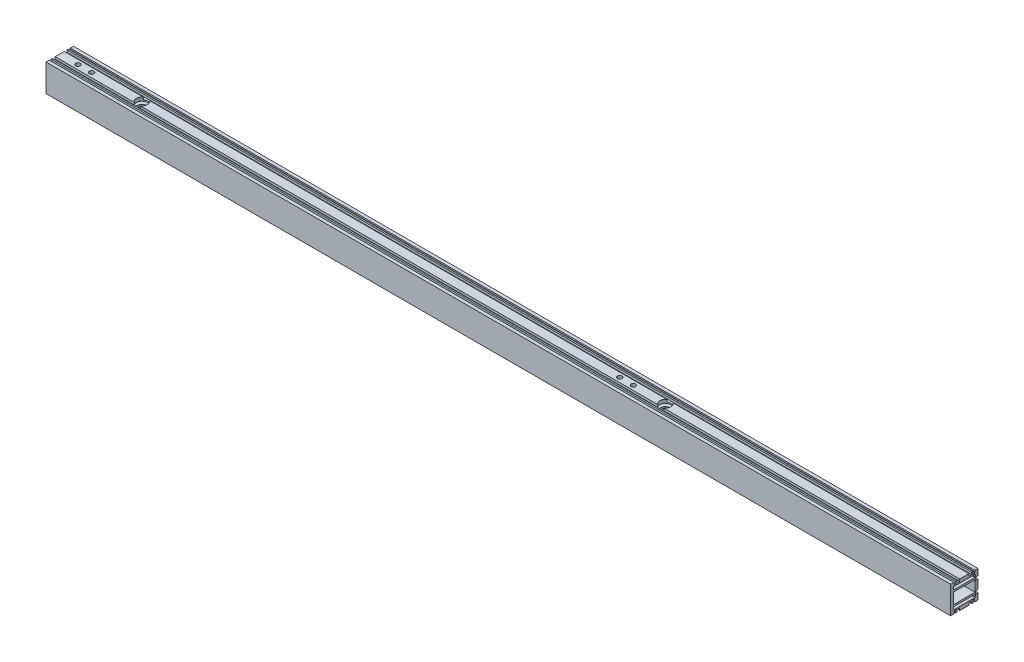
SolidWorks part; units mm, degrees
ref_plane "前视基准面" through (0, 0, 0) normal (0, 0, 1) x (1, 0, 0)
ref_plane "上视基准面" through (0, 0, 0) normal (0, 1, 0) x (1, 0, 0)
ref_plane "右视基准面" through (0, 0, 0) normal (1, 0, 0) x (0, 0, -1)
sketch "草图1" plane through (0, 0, 0) normal (1, 0, 0) x (0, 0, -1)
  line L0 (-15, 15) -> (15, -15) construction
  line L1 (-15, 15) -> (-11.5, 15)
  line L2 (-15, 15) -> (-15, -15)
  line L3 (-15, -15) -> (-11.5, -15)
  line L4 (15, 15) -> (15, 8)
  line L5 (15, 15) -> (-15, -15) construction
  line L6 (-11.5, 15) -> (-11.5, 13.5)
  line L7 (-11.5, 13.5) -> (-11, 13.5)
  line L8 (-11, 13.5) -> (-11, 12)
  line L9 (-11, 12) -> (-9.5, 12)
  line L10 (-9.5, 12) -> (-9.5, 15)
  line L11 (-9.5, 15) -> (-8, 15)
  line L12 (-8, 15) -> (-8, 12.5)
  line L13 (-8, 12.5) -> (-5, 12.5)
  line L14 (-5, 12.5) -> (-5, 15)
  line L15 (-5, 15) -> (5, 15)
  line L16 (0, 21.5201) -> (0, -18.309) construction
  line L17 (0, 55) -> (0, -55) construction
  line L18 (5, 12.5) -> (5, 15)
  line L19 (8, 12.5) -> (5, 12.5)
  line L20 (8, 15) -> (8, 12.5)
  line L21 (9.5, 15) -> (8, 15)
  line L22 (9.5, 12) -> (9.5, 15)
  line L23 (11, 12) -> (9.5, 12)
  line L24 (11, 13.5) -> (11, 12)
  line L25 (11.5, 13.5) -> (11, 13.5)
  line L26 (11.5, 15) -> (11.5, 13.5)
  line L27 (8, 15) -> (9.5, 15)
  line L28 (11.5, 15) -> (15, 15)
  line L29 (-19.8303, 0) -> (22.13, 0) construction
  line L30 (55, 0) -> (-55, 0) construction
  line L31 (8, -15) -> (9.5, -15)
  line L32 (11.5, -15) -> (11.5, -13.5)
  line L33 (11.5, -13.5) -> (11, -13.5)
  line L34 (11, -13.5) -> (11, -12)
  line L35 (11, -12) -> (9.5, -12)
  line L36 (9.5, -12) -> (9.5, -15)
  line L37 (9.5, -15) -> (8, -15)
  line L38 (8, -15) -> (8, -12.5)
  line L39 (8, -12.5) -> (5, -12.5)
  line L40 (5, -12.5) -> (5, -15)
  line L41 (-5, -15) -> (5, -15)
  line L42 (-5, -12.5) -> (-5, -15)
  line L43 (-8, -12.5) -> (-5, -12.5)
  line L44 (-8, -15) -> (-8, -12.5)
  line L45 (-9.5, -15) -> (-8, -15)
  line L46 (-9.5, -12) -> (-9.5, -15)
  line L47 (-11, -12) -> (-9.5, -12)
  line L48 (-11, -13.5) -> (-11, -12)
  line L49 (-11.5, -13.5) -> (-11, -13.5)
  line L50 (-11.5, -15) -> (-11.5, -13.5)
  line L51 (-9.5, -15) -> (-8, -15)
  line L52 (-5, -15) -> (5, -15)
  line L53 (8, -15) -> (9.5, -15)
  line L54 (11.5, -15) -> (15, -15)
  line L55 (15, 8) -> (12.5, 8)
  line L56 (12.5, 8) -> (12.5, 5)
  line L57 (12.5, 5) -> (15, 5)
  line L58 (12.5, -5) -> (15, -5)
  line L59 (12.5, -8) -> (12.5, -5)
  line L60 (15, -8) -> (12.5, -8)
  line L61 (15, 5) -> (15, -5)
  line L62 (15, -8) -> (15, -15)
  line L63 (12, -10.5) -> (12, -8.5)
  line L64 (-11.5, 11) -> (11.5, 11)
  line L65 (-12, 10.5) -> (-12, 8.5)
  line L66 (-11.5, 8) -> (11.5, 8)
  line L67 (12, 10.5) -> (12, 8.5)
  line L68 (-11.5, -8) -> (11.5, -8)
  line L69 (-12, -10.5) -> (-12, -8.5)
  line L70 (-11.5, -11) -> (11.5, -11)
  line L72 (-11.75, 6) -> (11.75, 6)
  line L73 (-11.75, 6) -> (-11.75, -6)
  line L74 (-11.75, -6) -> (11.75, -6)
  line L75 (11.75, 6) -> (11.75, -6)
  arc A0 (12, 8.5) -> (11.5, 8) centre (11.5, 8.5) cw
  arc A1 (11.5, 11) -> (12, 10.5) centre (11.5, 10.5) cw
  arc A2 (-11.5, 11) -> (-12, 10.5) centre (-11.5, 10.5) ccw
  arc A3 (-11.5, 8) -> (-12, 8.5) centre (-11.5, 8.5) cw
  arc A8 (-11.5, -8) -> (-12, -8.5) centre (-11.5, -8.5) ccw
  arc A9 (-11.5, -11) -> (-12, -10.5) centre (-11.5, -10.5) cw
  arc A10 (11.5, -11) -> (12, -10.5) centre (11.5, -10.5) ccw
  arc A11 (12, -8.5) -> (11.5, -8) centre (11.5, -8.5) ccw
  point P69 (12, 11)
  point P72 (-12, 11)
  point P77 (-11, -13.5)
  point P80 (11, -13.5)
  point P83 (11, 13.5)
  point P86 (-11, 13.5)
  point P99 (-12, -11)
  point P100 (12, -11)
  dimension "D17" = 0.5
  dimension "D1" = 3.5
  dimension "D2" = 1.5
  dimension "D3" = 0.5
  dimension "D4" = 1.5
  dimension "D5" = 3
  dimension "D6" = 30
  dimension "D7" = 30
  dimension "D8" = 1.5
  dimension "D9" = 2.5
  dimension "D10" = 3
  dimension "D11" = 2.5
  dimension "D12" = 7
  dimension "D13" = 3
  dimension "D14" = 4
  dimension "D15" = 3
  dimension "D16" = 24
  dimension "D19" = 23.5
  dimension "D20" = 12
extrude "凸台-拉伸1" add sketch "草图1" along normal mid plane 991 contours L2 L3 L50 L49 L48 L47 L46 L45 L44 L43 L42 L41 L40 L39 L38 L31 L36 L35 L34 L33 L32 L54 L62 L60 L59 L58 L61 L57 L56 L55 L4 L28 L26 L25 L24 L23 L22 L21 L20 L19 L18 L15 L14 L13 region at (0, 14.5757, 13.25)
hole_wizard "M6 螺纹孔1" positions "草图3" profile "草图2" tap size "M6" standard "GB"
sketch "草图3" plane through (0, -15, 0) normal (0, -1, 0) x (-1, 0, 0)
  point P0 (-445.5, 0)
  point P3 (-430.5, 0)
  point P6 (230.5, 0)
  point P9 (245.5, 0)
  point P12 (460.5, 0)
  point P15 (475.5, 0)
sketch "草图2" plane through (445.5, -15, 0) normal (1, 0, 0) x (0, 0, -1)
  line L0 (0, 0) -> (0, 20.5022)
  line L1 (0, 20.5022) -> (2.5, 19)
  line L2 (2.5, 19) -> (2.5, 0)
  line L5 (2.5, 0) -> (0, 0)
  line L10 (0, 20.5022) -> (-2.5, 19) construction
  line L11 (0, -6.35) -> (0, 107.95) construction
  dimension "螺纹孔钻头直径" = 5
  dimension "螺纹孔钻头深度" = 19
  dimension "导头角度" = 118
cosmetic thread "孔螺蚊线1" parameters "D1"=9, "D2"=6
cosmetic thread "孔螺蚊线2" parameters "D1"=9, "D2"=6
cosmetic thread "孔螺蚊线3" parameters "D1"=9, "D2"=6
cosmetic thread "孔螺蚊线4" parameters "D1"=9, "D2"=6
cosmetic thread "孔螺蚊线5" parameters "D1"=9, "D2"=6
cosmetic thread "孔螺蚊线6" parameters "D1"=9, "D2"=6
hole_wizard "M6 螺纹孔2" positions "草图5" profile "草图4" tap size "M6" standard "GB"
sketch "草图5" plane through (0, 0, -15) normal (0, 0, -1) x (-1, 0, 0)
  line L0 (-495.5, -15) -> (495.5, -15) construction
  line L1 (-495.5, 5) -> (-495.5, -5) construction
  line L2 (-495.5, 8) -> (-495.5, 5) construction
  point P0 (-445.5, 0)
  point P3 (-430.5, 0)
  point P7 (-370.5, 0)
  point P9 (-266.5, 0)
  point P18 (-394.5, 0)
  dimension "D1" = 15
  dimension "D2" = 15
  dimension "D3" = 104
  dimension "D4" = 125
  dimension "D5" = 101
  dimension "D10" = 15
sketch "草图4" plane through (445.5, 0, -15) normal (1, 0, 0) x (0, 1, 0)
  line L0 (0, 0) -> (0, 20.5022)
  line L1 (0, 20.5022) -> (2.5, 19)
  line L2 (2.5, 19) -> (2.5, 0)
  line L5 (2.5, 0) -> (0, 0)
  line L10 (0, 20.5022) -> (-2.5, 19) construction
  line L11 (0, -6.35) -> (0, 107.95) construction
  dimension "螺纹孔钻头直径" = 5
  dimension "螺纹孔钻头深度" = 19
  dimension "导头角度" = 118
cosmetic thread "孔螺蚊线7" parameters "D1"=3.25, "D2"=6
cosmetic thread "孔螺蚊线8" parameters "D1"=3.25, "D2"=6
cosmetic thread "孔螺蚊线13" parameters "D1"=3.25, "D2"=6
cosmetic thread "孔螺蚊线14" parameters "D1"=3.25, "D2"=6
cosmetic thread "孔螺蚊线17" parameters "D1"=3.25, "D2"=6
hole_wizard "M6 螺纹孔3" positions "草图7" profile "草图6" tap size "M6" standard "GB"
sketch "草图7" plane through (0, 15, 0) normal (0, 1, 0) x (1, 0, 0)
  point P0 (133, 0)
  point P3 (118, 0)
  point P6 (-460.5, 0)
  point P9 (-475.5, 0)
sketch "草图6" plane through (133, 15, 0) normal (1, 0, 0) x (0, 0, 1)
  line L0 (0, 0) -> (0, 20.5022)
  line L1 (0, 20.5022) -> (2.5, 19)
  line L2 (2.5, 19) -> (2.5, 0)
  line L5 (2.5, 0) -> (0, 0)
  line L10 (0, 20.5022) -> (-2.5, 19) construction
  line L11 (0, -6.35) -> (0, 107.95) construction
  dimension "螺纹孔钻头直径" = 5
  dimension "螺纹孔钻头深度" = 19
  dimension "导头角度" = 118
cosmetic thread "孔螺蚊线9" parameters "D1"=9, "D2"=6
cosmetic thread "孔螺蚊线10" parameters "D1"=9, "D2"=6
cosmetic thread "孔螺蚊线11" parameters "D1"=9, "D2"=6
cosmetic thread "孔螺蚊线12" parameters "D1"=9, "D2"=6
hole_wizard "Ø12.0 (12) 直径孔1" positions "草图9" profile "草图8" hole size "Ø12.0" standard "GB" end condition through all
sketch "草图9" plane through (0, -15, 0) normal (0, -1, 0) x (-1, 0, 0)
  line L0 (-495.5, 15) -> (495.5, 15) construction
  line L1 (495.5, 11.5) -> (495.5, 15) construction
  line L2 (-495.5, -5) -> (-495.5, 5) construction
  point P0 (-168, 0)
  point P2 (405.5, 0)
  dimension "D1" = 15
  dimension "D2" = 90
  dimension "D3" = 15
  dimension "D4" = 327.5
sketch "草图8" plane through (168, -15, 0) normal (1, 0, 0) x (0, 0, -1)
  line L0 (0, 0) -> (0, 30)
  line L1 (0, 30) -> (6, 30)
  line L2 (6, 30) -> (6, 0)
  line L5 (6, 0) -> (0, 0)
  line L11 (0, -6.35) -> (0, 107.95) construction
  dimension "通孔孔直径" = 12
  dimension "通孔孔深度" = 30
hole_wizard "M4 螺纹孔1" positions "草图11" profile "草图10" tap size "M4" standard "GB"
sketch "草图11" plane through (0, 0, -15) normal (0, 0, -1) x (-1, 0, 0)
  line L0 (-495.5, -15) -> (-171.3166, -15) construction
  line L1 (-495.5, 5) -> (-495.5, -5) construction
  point P0 (-341, 0)
  point P2 (-296, 0)
  point P4 (-236, 0)
  point P6 (-191, 0)
  dimension "D1" = 15
  dimension "D2" = 15
  dimension "D3" = 15
  dimension "D4" = 15
  dimension "D5" = 154.5
  dimension "D6" = 199.5
  dimension "D7" = 259.5
  dimension "D8" = 304.5
sketch "草图10" plane through (341, 0, -15) normal (1, 0, 0) x (0, 1, 0)
  line L0 (0, 0) -> (0, 12.4914)
  line L1 (0, 12.4914) -> (1.65, 11.5)
  line L2 (1.65, 11.5) -> (1.65, 0)
  line L5 (1.65, 0) -> (0, 0)
  line L10 (0, 12.4914) -> (-1.65, 11.5) construction
  line L11 (0, -6.35) -> (0, 107.95) construction
  dimension "螺纹孔钻头直径" = 3.3
  dimension "螺纹孔钻头深度" = 11.5
  dimension "导头角度" = 118
cosmetic thread "孔螺蚊线18" parameters "D1"=3.25, "D2"=4
cosmetic thread "孔螺蚊线19" parameters "D1"=3.25, "D2"=4
cosmetic thread "孔螺蚊线20" parameters "D1"=3.25, "D2"=4
cosmetic thread "孔螺蚊线21" parameters "D1"=3.25, "D2"=4
